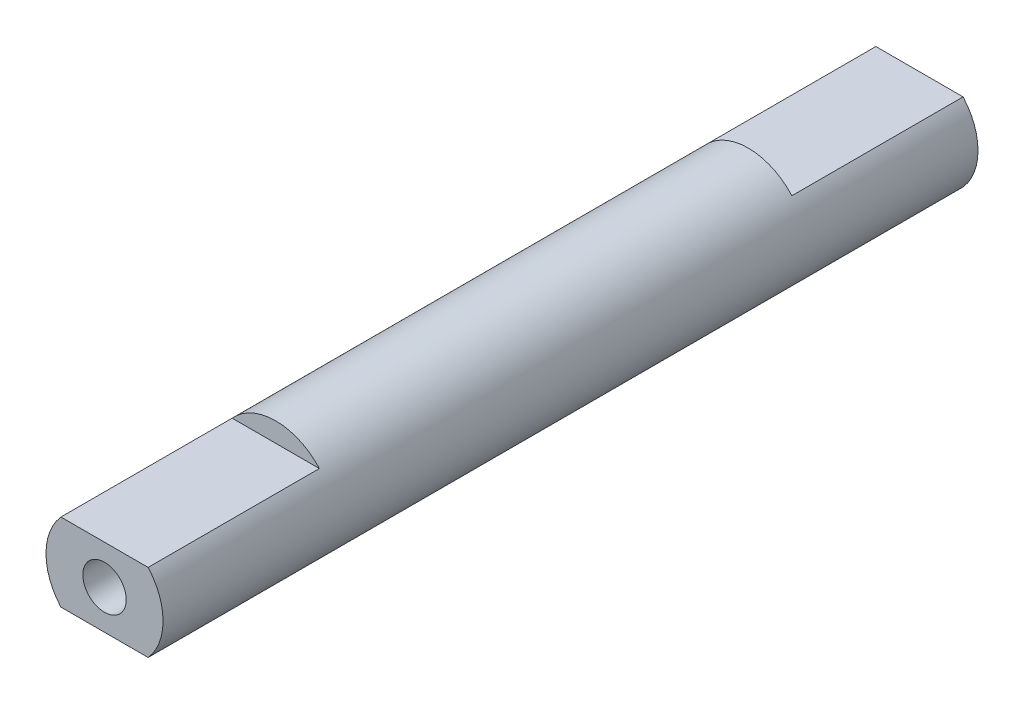
SolidWorks part; units mm, degrees
material "PBT General Purpose"
ref_plane "Alzado" through (0, 0, 0) normal (0, 0, 1) x (1, 0, 0)
ref_plane "Planta" through (0, 0, 0) normal (0, 1, 0) x (1, 0, 0)
ref_plane "Vista lateral" through (0, 0, 0) normal (1, 0, 0) x (0, 0, -1)
sketch "Croquis1" plane through (0, 0, 0) normal (0, 0, 1) x (1, 0, 0)
  circle A0 centre (0, 0) radius 2.7
  circle A1 centre (0, 0) radius 1
  dimension "D1" = 2.7
  dimension "D2" = 2
extrude "Saliente-Extruir1" add sketch "Croquis1" along normal mid plane 37.6 contours A0 A1 region at (-2.6236, 0, 0)
sketch "Croquis4" plane through (0, 0, -18.8) normal (0, 0, -1) x (-1, 0, 0)
  line L0 (-2.7, 0) -> (2.7, 0) construction
  line L1 (-2.0125, 1.8) -> (2.0125, 1.8)
  line L2 (-2.0125, -1.8) -> (2.0125, -1.8)
  circle A0 centre (0, 0) radius 2.7 construction
  arc A1 (-2.0125, -1.8) -> (2.0125, -1.8) centre (0, 0) ccw
  arc A2 (2.0125, 1.8) -> (-2.0125, 1.8) centre (0, 0) ccw
  dimension "D1" = 3.6
extrude "Cortar-Extruir2" cut sketch "Croquis4" against normal blind 7.9
mirror "Simetría1" about plane through (0, 0, 0) normal (0, 0, 1) of "Cortar-Extruir2"
